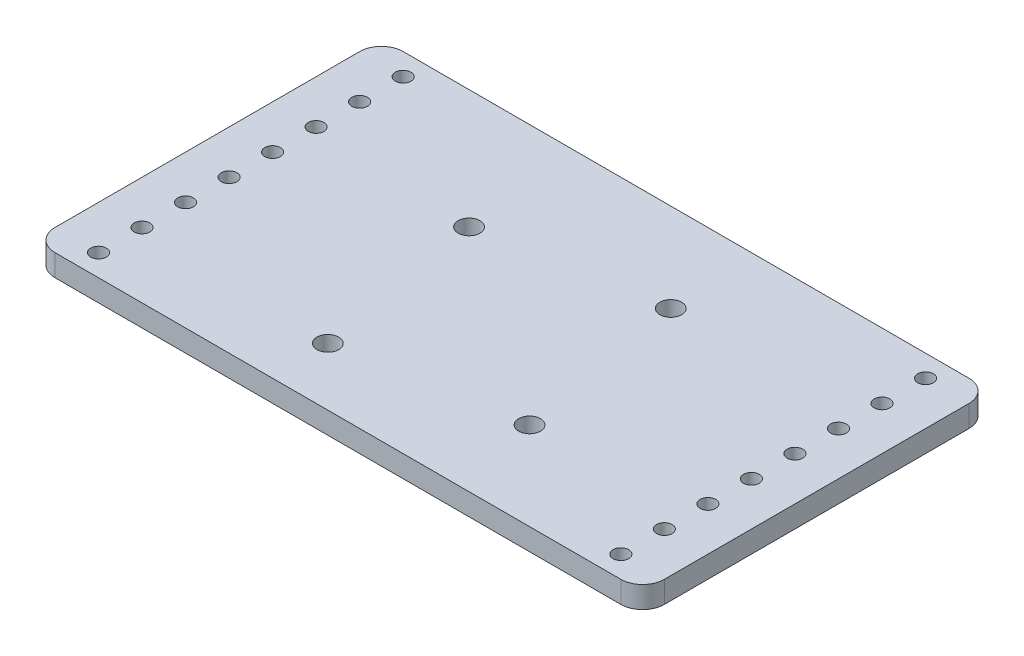
SolidWorks part; units mm, degrees
ref_plane "Front Plane" through (0, 0, 0) normal (0, 0, 1) x (1, 0, 0)
ref_plane "Top Plane" through (0, 0, 0) normal (0, 1, 0) x (1, 0, 0)
ref_plane "Right Plane" through (0, 0, 0) normal (1, 0, 0) x (0, 0, -1)
sketch "Sketch1" plane through (0, 0, 0) normal (0, 1, 0) x (1, 0, 0)
  line L1 (-88.9, -50.8) -> (88.9, -50.8)
  line L2 (-88.9, -50.8) -> (-88.9, 50.8)
  line L3 (-88.9, 50.8) -> (88.9, 50.8)
  line L4 (88.9, -50.8) -> (88.9, 50.8)
  line L5 (-88.9, -50.8) -> (88.9, 50.8) construction
  line L6 (-88.9, 50.8) -> (88.9, -50.8) construction
  point P0 (0, 0)
  dimension "D1" = 101.6
  dimension "D2" = 177.8
extrude "Initial Plate" add sketch "Sketch1" along normal blind 6.35
sketch "Sketch2" plane through (0, 6.35, 0) normal (0, 1, 0) x (1, 0, 0)
  line L0 (25.808, -0.0919) -> (-24.2202, -8.9132) construction
  line L1 (-19.8095, -33.9273) -> (-28.6309, 16.1009) construction
  line L2 (30.2187, -25.106) -> (21.3974, 24.9222) construction
  line L3 (-88.9, -50.8) -> (88.9, -50.8) construction
  line L4 (-27.5282, 9.8474) -> (-37.9796, 8.0045) construction
  line L5 (-20.9122, -27.6738) -> (-31.3636, -29.5167) construction
  line L6 (-25.4, 50.8) -> (-25.4, -50.8) construction
  line L7 (0, 0) -> (0.7939, -4.5025) construction
  line L8 (88.9, 50.8) -> (-88.9, 50.8) construction
  line L9 (-88.9, -50.8) -> (88.9, -50.8) construction
  circle A0 centre (-28.6309, 16.1009) radius 3.175
  circle A1 centre (-19.8095, -33.9273) radius 3.175
  circle A2 centre (30.2187, -25.106) radius 3.175
  circle A3 centre (21.3974, 24.9222) radius 3.175
  circle A4 centre (-28.6309, 16.1009) radius 6.35 construction
  circle A5 centre (-19.8095, -33.9273) radius 6.35 construction
  point P4 (0, 0)
  point P7 (-24.2202, -8.9132)
  point P10 (25.808, -0.0919)
  dimension "D5" = 6.35
  dimension "D3" = 12.7
  dimension "D6" = 38.1
  dimension "D1" = 50.8
  dimension "D2" = 90
  dimension "D4" = 10
  dimension "D8" = 4.572
  dimension "D9" = 25.4
extrude "Bearing Stack Holes" cut sketch "Sketch2" against normal through all
sketch "Sketch3" plane through (0, 6.35, 0) normal (0, 1, 0) x (1, 0, 0)
  line L0 (76.2, -44.45) -> (-76.2, -44.45) construction
  line L1 (0, 0) -> (0, -44.45) construction
  line L2 (-88.9, -50.8) -> (88.9, -50.8) construction
  line L3 (-88.9, 50.8) -> (-88.9, -50.8) construction
  circle A0 centre (-76.2, -44.45) radius 2.286
  circle A1 centre (76.2, -44.45) radius 2.286
  point P4 (0, 0)
  dimension "D1" = 4.572
  dimension "D2" = 6.35
  dimension "D3" = 12.7
extrude "Initial Mounting Hole" cut sketch "Sketch3" against normal through all
pattern_linear "Mounting Pattern" count 8 spacing 12.7 along (0, 0, -1) of "Initial Mounting Hole"
fillet "Fillet1" radius 6.35 4 edges at (88.9, 3.175, -50.8) (88.9, 3.175, 50.8) (-88.9, 3.175, 50.8) (-88.9, 3.175, -50.8)
